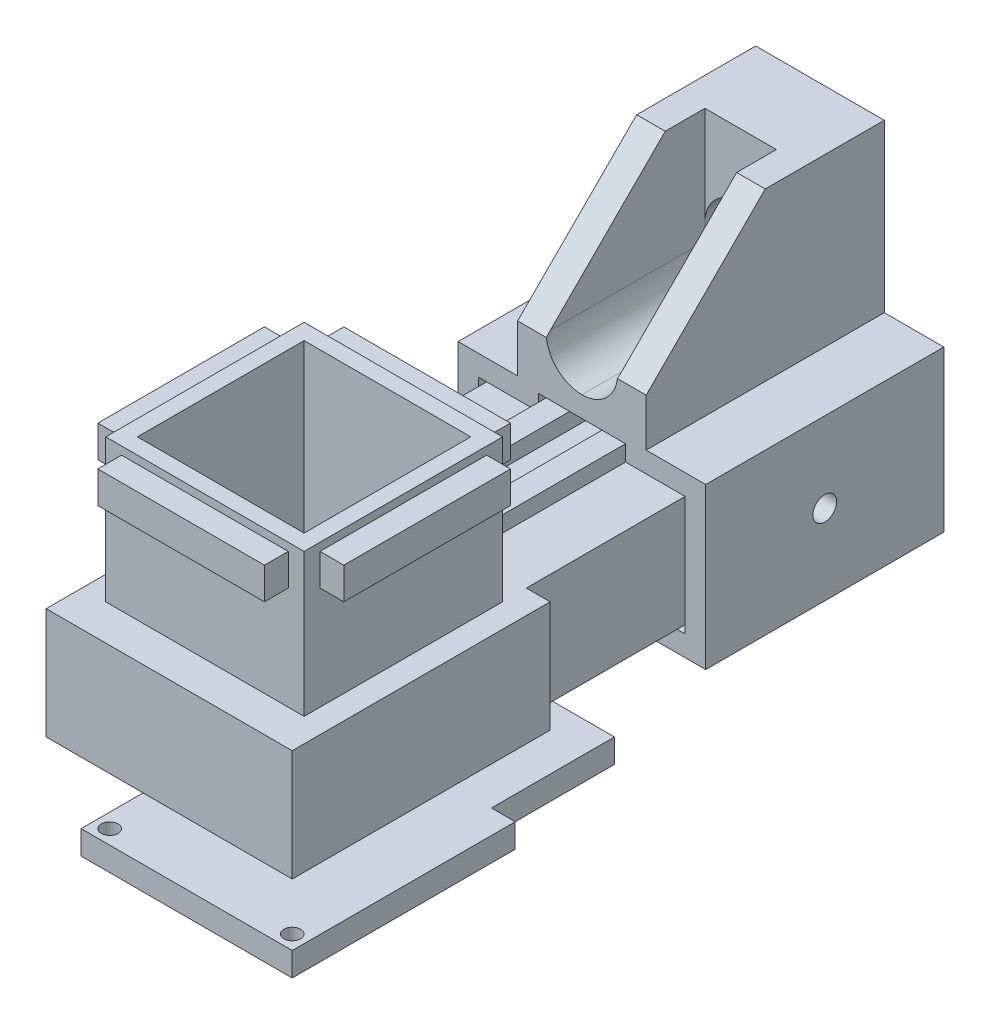
SolidWorks part; units mm, degrees
note: The reader was unsure of these and kept them because the rebuilt part matched: shared geometry of "Sketch2<3>", "Sketch3<7>", "Sketch3<12>", "Sketch3<16>", "Sketch6<3>", "Sketch3<14>", "Sketch14<5>", "Sketch14<7>", "Sketch14<8>".
ref_plane "Front Plane" through (0, 0, 0) normal (0, 0, 1) x (1, 0, 0)
ref_plane "Top Plane" through (0, 0, 0) normal (0, 1, 0) x (1, 0, 0)
ref_plane "Right Plane" through (0, 0, 0) normal (1, 0, 0) x (0, 0, -1)
sketch "Sketch2" plane through (0, 0, 0) normal (0, 1, 0) x (1, 0, 0)
  line L0 (10.5, 10.5) -> (10.5, -10.5)
  line L1 (-12.5, 12.5) -> (12.5, 12.5)
  line L2 (-12.5, 12.5) -> (-12.5, -12.5)
  line L3 (-12.5, -12.5) -> (12.5, -12.5)
  line L4 (12.5, 12.5) -> (12.5, -12.5)
  line L5 (-12.5, 12.5) -> (12.5, -12.5) construction
  line L6 (-12.5, -12.5) -> (12.5, 12.5) construction
  line L7 (-10.5, -10.5) -> (10.5, -10.5)
  line L8 (-10.5, 10.5) -> (-10.5, -10.5)
  line L9 (-10.5, 10.5) -> (10.5, 10.5)
  line L10 (-15.5, 15.5) -> (15.5, 15.5)
  line L11 (15.5, 15.5) -> (15.5, -15.5)
  line L12 (-15.5, -15.5) -> (15.5, -15.5)
  line L13 (-15.5, 15.5) -> (-15.5, -15.5)
  point P0 (0, 0)
  dimension "D1" = 25
  dimension "D2" = 25
  dimension "D3" = 2
  dimension "D4" = 3
extrude "Boss-Extrude1" add sketch "Sketch2" against normal blind 25 contours L4 L1 L2 L3 L8 L9 L0 L7
extrude "Boss-Extrude2" add sketch "Sketch2<3>" against normal blind 4 from offset 1 contours L10 L13 L12 L11 L1 L4 L3 L2 offset against normal yes
sketch "Sketch2<3>" plane through (0, 0, 0) normal (0, 1, 0) x (1, 0, 0) same geometry as "Sketch2"
sketch "Sketch3" plane through (0, -25, 0) normal (0, -1, 0) x (1, 0, 0)
  line L0 (0, 0) -> (0, -22.9057) construction
  line L1 (0, 15) -> (0, 0)
  line L2 (-10.5, 15) -> (10.5, 15)
  line L3 (-10.5, 15) -> (-10.5, -43)
  line L4 (-10.5, -43) -> (10.5, -43)
  line L5 (10.5, 15) -> (10.5, -43)
  line L6 (-12.5, 17) -> (-12.5, -45)
  line L7 (-12.5, -45) -> (12.5, -45)
  line L8 (12.5, 17) -> (12.5, -45)
  line L9 (-12.5, 17) -> (12.5, 17)
  line L10 (-12.5, 17) -> (-15.5, 17)
  line L11 (10.5, -17.5) -> (-10.5, -17.5)
  line L12 (10.5, -17.5) -> (10.5, -10.5)
  line L13 (10.5, -10.5) -> (-10.5, -10.5)
  line L14 (-10.5, -17.5) -> (-10.5, -10.5)
  line L15 (10.5, -17.5) -> (-10.5, -10.5) construction
  line L16 (10.5, -10.5) -> (-10.5, -17.5) construction
  line L19 (-10.5, -28) -> (10.5, -28)
  line L21 (-10.5, 10.5) -> (10.5, 10.5) construction
  line L22 (-10.5, -43) -> (10.5, -43)
  line L23 (-15.5, 17) -> (-15.5, 15.5)
  line L24 (12.5, 17) -> (15.5, 17)
  line L25 (15.5, 17) -> (15.5, 15.5)
  line L28 (15.5, 15.5) -> (-15.5, 15.5)
  line L34 (15.5, -15.5) -> (12.5, -15.5)
  line L35 (-15.5, -15.5) -> (-12.5, -15.5)
  line L36 (-1.5, -10.8377) -> (-1.5, -9.748)
  line L41 (1.5, -18.252) -> (-1.5, -18.252)
  line L42 (1.5, -18.252) -> (1.5, -17.1623)
  line L43 (1.5, -9.748) -> (-1.5, -9.748)
  line L44 (-1.5, -18.252) -> (-1.5, -17.1623)
  line L45 (1.5, -18.252) -> (-1.5, -9.748) construction
  line L46 (1.5, -9.748) -> (-1.5, -18.252) construction
  line L47 (1.5, -10.8377) -> (1.5, -9.748)
  line L48 (-10.5, -43) -> (-10.5, -41)
  line L49 (-10.5, -41) -> (10.5, -41)
  line L50 (10.5, -43) -> (10.5, -41)
  line L51 (-10.5, -43) -> (-8.5, -43)
  line L52 (-10.5, -43) -> (-10.5, -34)
  line L53 (-10.5, -34) -> (-8.5, -34)
  line L54 (-8.5, -43) -> (-8.5, -34)
  line L55 (-10.5, 10.5) -> (10.5, 10.5)
  line L57 (-8.5, -34) -> (-3.5, -34)
  line L58 (-8.5, -34) -> (-8.5, -41)
  line L59 (-8.5, -41) -> (-3.5, -41)
  line L60 (-15.5, -15.5) -> (15.5, -15.5)
  line L61 (15.5, -15.5) -> (15.5, 15.5)
  line L62 (15.5, -15.5) -> (15.5, 15.5)
  line L63 (-15.5, 15.5) -> (-15.5, -15.5)
  line L64 (-15.5, 15.5) -> (-15.5, -15.5)
  line L65 (-3.5, -34) -> (-3.5, -41)
  arc A0 (1.5, -17.1623) -> (1.5, -10.8377) centre (0, -14) ccw
  circle A1 centre (0, 2) radius 1
  arc A3 (-1.5, -10.8377) -> (-1.5, -17.1623) centre (0, -14) ccw
  point P24 (0.7389, -34.4855)
  point P36 (0, -10.5)
  point P46 (-1.5, -10.8377)
  line M11 (12.5, -12.5) -> (12.5, 12.5)
  line M12 (12.5, 12.5) -> (-12.5, 12.5)
  line M13 (-12.5, 12.5) -> (-12.5, -12.5)
  line M14 (-12.5, -12.5) -> (12.5, -12.5)
  line M16 (-10.5, 10.5) -> (10.5, 10.5)
  dimension "D4" = 7
  dimension "D6" = 2
  dimension "D9" = 2
  dimension "D1" = 15
  dimension "D2" = 58
  dimension "D3" = 21
  dimension "D5" = 29
  dimension "D7" = 13
  dimension "D10" = 2
  dimension "D11" = 9
  dimension "D12" = 5
  dimension "D17" = 3
  dimension "D18" = 8.504
  dimension "D8" = 2
  dimension "D16" = 0
extrude "Boss-Extrude4" add sketch "Sketch3" against normal blind 7
extrude "Cut-Extrude2" cut sketch "Sketch3<7>" against normal blind 6 contours L41 L44 A3 L36 L43 L47 A0 L42
sketch "Sketch3<7>" plane through (0, -25, 0) normal (0, -1, 0) x (1, 0, 0) same geometry as "Sketch3"
extrude "Boss-Extrude5" add sketch "Sketch3<12>" along normal blind 4 contours L9 L6 L7 L8 L2 L5 L4 L3 M12 M11 M14 M13 | L3 M12 M13 M14 | L5 M12 M14 M11 | L64 L35 L6 L10 L23 | L34 L62 L25 L24 L8 | L9 L6 L3 L2 L5 L8 M12
sketch "Sketch3<12>" plane through (0, -25, 0) normal (0, -1, 0) x (1, 0, 0) same geometry as "Sketch3"
extrude "Cut-Extrude12" cut sketch "Sketch3<16>" against normal blind 1 contours L3 L55 L1 M16 M12 | L2 L3 L1 M12
sketch "Sketch3<16>" plane through (0, -25, 0) normal (0, -1, 0) x (1, 0, 0) same geometry as "Sketch3"
sketch "Sketch6" plane through (0, -29, 0) normal (0, -1, 0) x (1, 0, 0)
  line L0 (13.5, 15) -> (-13.5, 15)
  line L1 (-13.5, 15) -> (-13.5, -13.5)
  line L2 (-13.5, -13.5) -> (-10.5, -13.5)
  line L3 (-10.5, -13.5) -> (-10.5, -43)
  line L4 (-10.5, -43) -> (10.5, -43)
  line L5 (10.5, -43) -> (10.5, -13.5)
  line L6 (10.5, -13.5) -> (13.5, -13.5)
  line L7 (13.5, -13.5) -> (13.5, 15)
  line L8 (15.5, 17) -> (-15.5, 17)
  line L11 (-12.5, -15.5) -> (-12.5, -45)
  line L12 (-12.5, -45) -> (12.5, -45)
  line L13 (12.5, -45) -> (12.5, -15.5)
  line L16 (15.5, 17) -> (-15.5, 17)
  line L19 (-12.5, -15.5) -> (-12.5, -45)
  line L20 (-12.5, -45) -> (12.5, -45)
  line L21 (12.5, -45) -> (12.5, -15.5)
  line L25 (-13.5, 15) -> (-9.5, 15)
  line L26 (-13.5, 15) -> (-13.5, 11)
  line L27 (-13.5, 11) -> (-9.5, 11)
  line L28 (-9.5, 15) -> (-9.5, 11)
  line L29 (13.5, 15) -> (9.5, 15)
  line L30 (13.5, 15) -> (13.5, 11)
  line L31 (13.5, 11) -> (9.5, 11)
  line L32 (9.5, 15) -> (9.5, 11)
  line L36 (-15.5, 17) -> (-15.5, -15.5)
  line L37 (-15.5, 17) -> (-15.5, -15.5)
  line L38 (-15.5, -15.5) -> (-12.5, -15.5)
  line L39 (-15.5, -15.5) -> (-12.5, -15.5)
  line L40 (-15.5, 17) -> (-15.5, -15.5) construction
  line L41 (-15.5, -15.5) -> (-12.5, -15.5) construction
  line L42 (12.5, -15.5) -> (15.5, -15.5) construction
  line L43 (15.5, -15.5) -> (15.5, 17) construction
  line L44 (12.5, -15.5) -> (15.5, -15.5)
  line L45 (12.5, -15.5) -> (15.5, -15.5)
  line L46 (15.5, -15.5) -> (15.5, 17)
  line L47 (15.5, -15.5) -> (15.5, 17)
  line M17 (10.5, 15) -> (10.5, -43)
  line M18 (10.5, -43) -> (-10.5, -43)
  line M19 (-10.5, -43) -> (-10.5, 15)
  line M20 (-10.5, 15) -> (10.5, 15)
  line M21 (15.5, 17) -> (-15.5, 17)
  line M22 (-15.5, 17) -> (-15.5, -15.5)
  line M23 (-15.5, -15.5) -> (-12.5, -15.5)
  line M24 (-12.5, -15.5) -> (-12.5, -45)
  line M25 (-12.5, -45) -> (12.5, -45)
  line M26 (12.5, -45) -> (12.5, -15.5)
  line M27 (12.5, -15.5) -> (15.5, -15.5)
  line M28 (15.5, -15.5) -> (15.5, 17)
  dimension "D3" = 4
  dimension "D4" = 4
  dimension "D5" = 4
  dimension "D6" = 4
  dimension "D1" = 0
  dimension "D2" = 2
extrude "Boss-Extrude7" add sketch "Sketch6" against normal blind 6 contours L28 L27 M20 M19 | L32 L31 M20 M17
extrude "Boss-Extrude8" add sketch "Sketch6<3>" along normal blind 3 contours L7 L6 L2 L1 L0 M28 M21 M22 M23 M24 M25 M26 M27 M17 M18 M19 M20
sketch "Sketch6<3>" plane through (0, -29, 0) normal (0, -1, 0) x (1, 0, 0) same geometry as "Sketch6"
sketch "Sketch7" plane through (0, -29, 0) normal (0, -1, 0) x (1, 0, 0)
  line L0 (13.5, -13.5) -> (13.5, 15) construction
  line L1 (13.5, 15) -> (9.5, 15) construction
  line L2 (9.5, 15) -> (9.5, 11) construction
  line L3 (9.5, 11) -> (10.5, 11) construction
  line L4 (10.5, 11) -> (10.5, -13.5) construction
  line L5 (10.5, -13.5) -> (13.5, -13.5) construction
  line L6 (-9.5, 11) -> (-9.5, 15) construction
  line L7 (-9.5, 15) -> (-13.5, 15) construction
  line L8 (-13.5, 15) -> (-13.5, -13.5) construction
  line L9 (-13.5, -13.5) -> (-10.5, -13.5) construction
  line L10 (-10.5, -13.5) -> (-10.5, 11) construction
  line L11 (-10.5, 11) -> (-9.5, 11) construction
  line L12 (13.5, -13.5) -> (13.5, 15)
  line L13 (13.5, 15) -> (9.5, 15)
  line L14 (9.5, 15) -> (9.5, 11)
  line L15 (9.5, 11) -> (10.5, 11)
  line L16 (10.5, 11) -> (10.5, -13.5)
  line L17 (10.5, -13.5) -> (13.5, -13.5)
  line L18 (-9.5, 11) -> (-9.5, 15)
  line L19 (-9.5, 15) -> (-13.5, 15)
  line L20 (-13.5, 15) -> (-13.5, -13.5)
  line L21 (-13.5, -13.5) -> (-10.5, -13.5)
  line L22 (-10.5, -13.5) -> (-10.5, 11)
  line L23 (-10.5, 11) -> (-9.5, 11)
  line L24 (-9.5, 11) -> (-13.5, 15) construction
  line L25 (9.5, 11) -> (13.5, 15) construction
  circle A0 centre (-11.5, 13) radius 1.05
  circle A1 centre (11.5, 13) radius 1.05
  dimension "D1" = 2.1
  dimension "D2" = 2.1
extrude "Cut-Extrude9" cut sketch "Sketch7" against normal blind 3 contours A0 | A1
extrude "Cut-Extrude11" cut sketch "Sketch3<14>" against normal blind 3 contours L41 L44 L11 L3 L19 L5 L42 | L54 L49 L5 L19 L3 L53
sketch "Sketch3<14>" plane through (0, -25, 0) normal (0, -1, 0) x (1, 0, 0) same geometry as "Sketch3"
sketch "Sketch10" plane through (0, -25, 0) normal (0, -1, 0) x (1, 0, 0)
  line L1 (10.5, -43) -> (-10.5, -43) construction
  line L6 (-10.5, -34) -> (-8.5, -34)
  line L18 (-10.5, -34) -> (-10.5, -43)
  line L19 (-10.5, -43) -> (-8.5, -43)
  line L21 (-8.5, -34) -> (-8.5, -43)
  line L24 (-3.5, -34) -> (-3.5, -41) construction
  line M11 (-3.5, -34) -> (-10.5, -34)
  line M12 (-10.5, -34) -> (-10.5, -43)
  line M13 (-10.5, -43) -> (10.5, -43)
  dimension "D1" = 5
extrude "Boss-Extrude12" add sketch "Sketch10" along normal up to surface (4 mm away) contours L21 M11 M12 M13 up to face at (-11.5, -29, 11.95)
ref_plane "Plane1" through (0, -42, 0) normal (0, -1, 0) x (-1, 0, 0)
sketch "Sketch8" plane through (0, -42, 0) normal (0, -1, 0) x (-1, 0, 0)
  line L8 (-15.5, 15.5) -> (-15.5, -17)
  line L10 (-15.5, 15.5) -> (-15.5, -17)
  line L12 (-15.5, -17) -> (15.5, -17)
  line L14 (-15.5, -17) -> (15.5, -17)
  line L24 (-13.3, -14.8) -> (13.3, -14.8)
  line L25 (13.3, -14.8) -> (13.3, 13.3)
  line L26 (13.3, 13.3) -> (10.3, 13.3)
  line L27 (10.3, 13.3) -> (10.3, 42.8)
  line L28 (10.3, 42.8) -> (-10.3, 42.8)
  line L29 (-10.3, 42.8) -> (-10.3, 13.3)
  line L30 (-10.3, 13.3) -> (-13.3, 13.3)
  line L31 (-13.3, 13.3) -> (-13.3, -14.8)
  line L32 (15.5, -17) -> (15.5, 15.5)
  line L34 (15.5, -17) -> (15.5, 15.5)
  line L36 (15.5, 15.5) -> (12.5, 15.5)
  line L38 (15.5, 15.5) -> (12.5, 15.5)
  line L40 (12.5, 15.5) -> (12.5, 45)
  line L41 (12.5, 15.5) -> (12.5, 45)
  line L42 (12.5, 45) -> (-12.5, 45)
  line L43 (12.5, 45) -> (-12.5, 45)
  line L44 (-12.5, 45) -> (-12.5, 15.5)
  line L45 (-12.5, 45) -> (-12.5, 15.5)
  line L46 (-12.5, 15.5) -> (-15.5, 15.5)
  line L47 (-12.5, 15.5) -> (-15.5, 15.5)
  line L49 (-10.3, 42.8) -> (6.8, 42.8)
  line L50 (-10.3, 42.8) -> (-10.3, 28.8)
  line L51 (-10.3, 28.8) -> (6.8, 28.8)
  line L60 (6.8, 42.8) -> (6.8, 28.8)
  circle A0 centre (-11.5, -13) radius 1.05 construction
  circle A1 centre (11.5, -13) radius 1.05 construction
  circle A2 centre (-11.5, -13) radius 1.05
  circle A3 centre (11.5, -13) radius 1.05
  dimension "D4" = 14
  dimension "D5" = 3.5
  dimension "D1" = 0
  dimension "D2" = 2.2
extrude "Boss-Extrude9" add sketch "Sketch8" along normal blind 3 separate body contours L28 L60 L51 L29 L30 L31 L24 L25 L26 L27 A3 A2
sketch "Sketch9" plane through (0, 0, -45) normal (0, 0, -1) x (-1, 0, 0)
  line L1 (6.5, -32) -> (-8.5, -32)
  line L2 (6.5, -32) -> (6.5, -26)
  line L3 (6.5, -26) -> (-8.5, -26)
  line L5 (10.5, -32) -> (10.5, -29)
  line L6 (-10.5, -32) -> (10.5, -32)
  line L7 (-10.5, -25) -> (-10.5, -32)
  line L9 (10.5, -32) -> (10.5, -29)
  line L10 (-10.5, -32) -> (10.5, -32)
  line L11 (-10.5, -25) -> (-10.5, -32)
  line L12 (-8.5, -32) -> (-8.5, -26)
  line L17 (8.5, -25) -> (-10.5, -25)
  line L18 (8.5, -25) -> (-10.5, -25)
  line L22 (10.5, -29) -> (8.5, -29)
  line L24 (10.5, -29) -> (8.5, -29)
  line L25 (8.5, -29) -> (8.5, -25)
  line L26 (8.5, -29) -> (8.5, -25)
  line M10 (-12.5, -32) -> (12.5, -32)
  dimension "D2" = 2
  dimension "D3" = 15
  dimension "D4" = 6
  dimension "D1" = 0
extrude "Cut-Extrude10" cut sketch "Sketch9" against normal up to surface (2 mm away) contours L12 L2 L3 M10 up to face at (-2.8333, -28.6667, -43)
sketch "Sketch11" plane through (0, -1, 0) normal (0, 1, 0) x (1, 0, 0)
  line L0 (-12.5, 12.5) -> (-12.5, -12.5) construction
  line L4 (15.5, 15.5) -> (-15.5, 15.5)
  line L5 (-15.5, 15.5) -> (-15.5, -15.5)
  line L6 (-15.5, -15.5) -> (15.5, -15.5)
  line L7 (15.5, -15.5) -> (15.5, 15.5)
  line L8 (15.5, 15.5) -> (-15.5, 15.5)
  line L9 (-15.5, 15.5) -> (-15.5, -15.5)
  line L10 (-15.5, -15.5) -> (15.5, -15.5)
  line L11 (15.5, -15.5) -> (15.5, 15.5)
  line L13 (-15.5, 15.5) -> (-12.5, 15.5)
  line L14 (-15.5, 15.5) -> (-15.5, 10.5)
  line L15 (-15.5, 10.5) -> (-12.5, 10.5)
  line L16 (-12.5, 15.5) -> (-12.5, 10.5)
  line L17 (-12.5, 12.5) -> (12.5, 12.5) construction
  line L18 (-15.5, 15.5) -> (-10.5, 15.5)
  line L19 (-15.5, 15.5) -> (-15.5, 12.5)
  line L20 (-15.5, 12.5) -> (-10.5, 12.5)
  line L21 (-10.5, 15.5) -> (-10.5, 12.5)
  line L22 (15.5, 15.5) -> (12.5, 15.5)
  line L23 (15.5, 15.5) -> (15.5, 10.5)
  line L24 (15.5, 10.5) -> (12.5, 10.5)
  line L25 (12.5, 15.5) -> (12.5, 10.5)
  line L26 (15.5, 15.5) -> (10.5, 15.5)
  line L27 (15.5, 15.5) -> (15.5, 12.5)
  line L28 (15.5, 12.5) -> (10.5, 12.5)
  line L29 (10.5, 15.5) -> (10.5, 12.5)
  line L30 (15.5, -15.5) -> (15.5, -12.5)
  line L31 (15.5, -15.5) -> (10.5, -15.5)
  line L32 (10.5, -15.5) -> (10.5, -12.5)
  line L33 (15.5, -12.5) -> (10.5, -12.5)
  line L34 (15.5, -15.5) -> (15.5, -10.5)
  line L35 (15.5, -15.5) -> (12.5, -15.5)
  line L36 (12.5, -15.5) -> (12.5, -10.5)
  line L37 (15.5, -10.5) -> (12.5, -10.5)
  line L38 (-15.5, -15.5) -> (-12.5, -15.5)
  line L39 (-15.5, -15.5) -> (-15.5, -10.5)
  line L40 (-15.5, -10.5) -> (-12.5, -10.5)
  line L41 (-12.5, -15.5) -> (-12.5, -10.5)
  line L42 (-15.5, -15.5) -> (-10.5, -15.5)
  line L43 (-15.5, -15.5) -> (-15.5, -12.5)
  line L44 (-15.5, -12.5) -> (-10.5, -12.5)
  line L45 (-10.5, -15.5) -> (-10.5, -12.5)
  point P39 (0, 0)
  line M20 (-12.5, 12.5) -> (12.5, 12.5)
  line M21 (12.5, 12.5) -> (12.5, -12.5)
  line M22 (12.5, -12.5) -> (-12.5, -12.5)
  line M23 (-12.5, -12.5) -> (-12.5, 12.5)
  line M24 (15.5, 15.5) -> (-15.5, 15.5)
  line M25 (-15.5, 15.5) -> (-15.5, -15.5)
  line M26 (-15.5, -15.5) -> (15.5, -15.5)
  line M27 (15.5, -15.5) -> (15.5, 15.5)
  dimension "D2" = 5
  dimension "D3" = 5
  dimension "D1" = 0
  dimension "D4" = 4
extrude "Cut-Extrude13" cut sketch "Sketch11" against normal up to surface (4 mm away) contours L44 L39 L41 M26 | L10 L45 L41 M22 | L44 L40 M25 M23 | L10 L36 L32 M22 | L36 L31 L33 M27 | L11 L37 L33 M21 | L20 L14 L15 M23 | L20 L16 L8 M25 | L21 L8 L16 M20 | L8 L29 L25 M20 | L28 L23 L25 M24 | L11 L28 L24 M21 up to face at (0, -5, 0)
sketch "Sketch12" plane through (0, 0, -45) normal (0, 0, -1) x (-1, 0, 0)
  line L0 (0, -32) -> (0, -5.0487) construction
  line L7 (-2.0407, -16) -> (2.0407, -16)
  line L8 (6.5, -26) -> (6.5, -32)
  line L9 (6.5, -32) -> (12.5, -32)
  line L10 (12.5, -32) -> (12.5, -18)
  line L11 (12.5, -18) -> (-12.5, -18)
  line L12 (-12.5, -18) -> (-12.5, -32)
  line L13 (-12.5, -32) -> (-8.5, -32)
  line L14 (-8.5, -32) -> (-8.5, -26)
  line L15 (-8.5, -26) -> (6.5, -26)
  line L16 (6.5, -26) -> (6.5, -32)
  line L17 (6.5, -32) -> (12.5, -32)
  line L18 (12.5, -32) -> (12.5, -18)
  line L19 (12.5, -18) -> (-12.5, -18)
  line L20 (-12.5, -18) -> (-12.5, -32)
  line L21 (-12.5, -32) -> (-8.5, -32)
  line L22 (-8.5, -32) -> (-8.5, -26)
  line L23 (-8.5, -26) -> (6.5, -26)
  line L27 (-2.0407, -16) -> (-2.0407, -18)
  line L28 (-2.0407, -18) -> (2.0407, -18)
  line L29 (2.0407, -16) -> (2.0407, -18)
  line L30 (-2.0407, -16) -> (2.0407, -18) construction
  line L31 (-2.0407, -18) -> (2.0407, -16) construction
  line L32 (-5, -16) -> (5, -16)
  line L33 (-5, -16) -> (-5, -18)
  line L34 (-5, -18) -> (5, -18)
  line L35 (5, -16) -> (5, -18)
  line L36 (-5, -16) -> (5, -18) construction
  line L37 (-5, -18) -> (5, -16) construction
  point P6 (0, -17)
  point P8 (0, -17)
  dimension "D2" = 2
  dimension "D3" = 10
  dimension "D1" = 0
extrude "Boss-Extrude13" add sketch "Sketch12" against normal up to surface (29.5 mm away) up to face at (-14, -25, -15.5)
ref_plane "Plane3" through (0, 0, -65) normal (0, 0, -1) x (-1, 0, 0)
sketch "Sketch13" plane through (0, 0, -65) normal (0, 0, -1) x (-1, 0, 0)
  line L0 (-8.5, -32) -> (6.5, -32)
  line L2 (6.5, -32.5) -> (13, -32.5)
  line L3 (13, -32.5) -> (13, -17.5)
  line L4 (13, -17.5) -> (5.5, -17.5)
  line L5 (-5.1, -10.9) -> (-5, -10.9)
  line L6 (5.5, -17.5) -> (5.5, -15.5)
  line L7 (5.5, -15.5) -> (1.5407, -15.5)
  line L11 (1.5407, -15.5) -> (-5.5, -15.5)
  line L12 (-5.5, -15.5) -> (-5.5, -17.5)
  line L13 (-5.5, -17.5) -> (-13, -17.5)
  line L14 (-13, -17.5) -> (-13, -32.5)
  line L15 (-13, -32.5) -> (-8.5, -32.5)
  line L16 (6.5, -26) -> (6.5, -32)
  line L17 (6.5, -32) -> (12.5, -32)
  line L18 (12.5, -32) -> (12.5, -18)
  line L19 (12.5, -18) -> (5, -18)
  line L20 (5, -18) -> (5, -16)
  line L26 (5, -18) -> (5, -16)
  line L27 (-5, -18) -> (-12.5, -18)
  line L28 (-12.5, -18) -> (-12.5, -32)
  line L29 (-12.5, -32) -> (-8.5, -32)
  line L30 (-8.5, -32) -> (-8.5, -26)
  line L31 (-8.5, -26) -> (6.5, -26)
  line L33 (6.5, -32) -> (12.5, -32)
  line L34 (12.5, -32) -> (12.5, -18)
  line L35 (12.5, -18) -> (5, -18)
  line L43 (-5, -18) -> (-12.5, -18)
  line L44 (-12.5, -18) -> (-12.5, -32)
  line L45 (-12.5, -32) -> (-8.5, -32)
  line L48 (-8.5, -32.5) -> (6.5, -32.5)
  line L49 (6.5, -35.1) -> (15.6, -35.1)
  line L50 (6.5, -32.1) -> (12.6, -32.1)
  line L51 (12.6, -32.1) -> (12.6, -17.9)
  line L52 (12.6, -17.9) -> (5.1, -17.9)
  line L58 (-5.1, -17.9) -> (-12.6, -17.9)
  line L59 (-12.6, -17.9) -> (-12.6, -32.1)
  line L60 (-12.6, -32.1) -> (-8.5, -32.1)
  line L61 (-8.5, -32.1) -> (6.5, -32.1)
  line L62 (6.5, -35.1) -> (15.6, -35.1)
  line L63 (15.6, -35.1) -> (15.6, -14.9)
  line L71 (-15.6, -14.9) -> (-15.6, -35.1)
  line L72 (-15.6, -35.1) -> (-8.5, -35.1)
  line L73 (-8.5, -35.1) -> (6.5, -35.1)
  line L74 (15.6, -35.1) -> (15.6, -14.9)
  line L75 (15.6, -14.9) -> (8.1, -14.9)
  line L76 (8.1, -14.9) -> (8.1, -12.9)
  line L77 (8.1, -12.9) -> (0, -12.9)
  line L78 (0, -12.9) -> (0, -12.9)
  line L79 (0, -12.9) -> (0, -12.9)
  line L80 (0, -12.9) -> (0, -12.9)
  line L81 (0, -12.9) -> (-8.1, -12.9)
  line L82 (-8.1, -12.9) -> (-8.1, -14.9)
  line L83 (-8.1, -14.9) -> (-15.6, -14.9)
  line L84 (-15.6, -14.9) -> (-15.6, -35.1)
  line L85 (-15.6, -35.1) -> (-8.5, -35.1)
  line L86 (-8.5, -35.1) -> (6.5, -35.1)
  line L87 (-1.5407, -15.5) -> (-5.5, -15.5) construction
  line L90 (5, -18) -> (5, -13) construction
  line L91 (5, -13) -> (3, -13) construction
  line L92 (-3, -13) -> (-5, -13) construction
  line L93 (-5, -13) -> (-5, -18) construction
  line L94 (5, -16) -> (2.0407, -16)
  line L95 (5, -16) -> (2.0407, -16)
  line L96 (2.0407, -16) -> (2.0407, -18)
  line L97 (2.0407, -16) -> (2.0407, -18)
  line L98 (2.0407, -18) -> (-2.0407, -18)
  line L99 (2.0407, -18) -> (-2.0407, -18)
  line L100 (-2.0407, -18) -> (-2.0407, -16)
  line L101 (-2.0407, -18) -> (-2.0407, -16)
  line L102 (-2.0407, -16) -> (-5, -16)
  line L103 (-2.0407, -16) -> (-5, -16)
  line L104 (-5, -16) -> (-5, -18)
  line L105 (-5, -16) -> (-5, -18)
  line L106 (-8.1, -9.9) -> (-8.1, -14.9) construction
  line L107 (-3, -9.9) -> (-8.1, -9.9) construction
  line L108 (-3, -9.9) -> (3, -9.9) construction
  line L109 (8.1, -9.9) -> (3, -9.9) construction
  line L110 (8.1, -14.9) -> (8.1, -9.9) construction
  line L111 (-3, -13) -> (3, -13) construction
  line L112 (5.1, -17.9) -> (5.1, -12.9) construction
  line L113 (5.1, -12.9) -> (3, -12.9) construction
  line L114 (-3, -12.9) -> (3, -12.9) construction
  line L115 (-3, -12.9) -> (-5.1, -12.9) construction
  line L116 (-5.1, -12.9) -> (-5.1, -17.9) construction
  line L117 (-8.1, -14.9) -> (-15.6, -14.9) construction
  line L118 (15.6, -14.9) -> (8.1, -14.9) construction
  line L119 (1.5407, -17.5) -> (-1.5407, -17.5) construction
  line L120 (1.5407, -15.5) -> (1.5407, -17.5) construction
  line L121 (-1.5407, -17.5) -> (-1.5407, -15.5) construction
  dimension "D1" = 0
  dimension "D2" = 0.1
  dimension "D3" = 3.1
  dimension "D4" = 0.5
  dimension "D5" = 3.1
extrude "Boss-Extrude14" add sketch "Sketch13" against normal blind 30 separate body
sketch "Sketch14" plane through (0, 0, -65) normal (0, 0, -1) x (-1, 0, 0)
  line L0 (0, -4.9) -> (0, 10.1531) construction
  line L1 (0, -6.4) -> (4.5, -6.4) construction
  line L3 (-8.1, 6.1) -> (8.1, 6.1)
  line L4 (-8.1, 6.1) -> (-8.1, -12.9)
  line L5 (-8.1, -12.9) -> (8.1, -12.9)
  line L6 (8.1, 6.1) -> (8.1, -12.9)
  line L7 (-8.1, 6.1) -> (8.1, -12.9) construction
  line L8 (-15.6, -35.1) -> (15.6, -35.1)
  line L9 (15.6, -35.1) -> (15.6, -14.9)
  line L10 (-8.1, -12.9) -> (-8.1, -14.9)
  line L11 (-8.1, -12.9) -> (-8.1, -14.9)
  line L12 (-8.1, -14.9) -> (-15.6, -14.9)
  line L13 (-8.1, -14.9) -> (-15.6, -14.9)
  line L14 (15.6, -14.9) -> (8.1, -14.9)
  line L15 (-15.6, -14.9) -> (-15.6, -35.1)
  line L16 (-15.6, -35.1) -> (15.6, -35.1)
  line L17 (15.6, -35.1) -> (15.6, -14.9)
  line L23 (-15.6, -14.9) -> (-15.6, -35.1)
  line L24 (-8.1, -12.9) -> (8.1, 6.1) construction
  line L32 (15.6, -14.9) -> (8.1, -14.9)
  line L33 (8.1, -14.9) -> (8.1, -12.9)
  line L34 (8.1, -14.9) -> (8.1, -12.9)
  line L35 (8.1, -12.9) -> (-8.1, -12.9)
  line L36 (8.1, -12.9) -> (-8.1, -12.9)
  circle A0 centre (0, -6.4) radius 2.6
  circle A1 centre (0, -6.4) radius 4.5
  circle A2 centre (4.5, -6.4) radius 1.1
  circle A3 centre (-4.5, -6.4) radius 1.1
  point P19 (0, -3.4)
  dimension "D2" = 5.2
  dimension "D3" = 9
  dimension "D4" = 2.2
  dimension "D5" = 4.5
  dimension "D6" = 16.2
  dimension "D7" = 12.5
  dimension "D8" = 6.5
  dimension "D1" = 0
extrude "Boss-Extrude16" add sketch "Sketch14" against normal blind 10 contours L4 L3 L6 L5
extrude "Cut-Extrude14" cut sketch "Sketch14<5>" against normal blind 3 contours A3 A1 | A3 A1 | A1 A2 | A1 A2
sketch "Sketch14<5>" plane through (0, 0, -65) normal (0, 0, -1) x (-1, 0, 0) same geometry as "Sketch14"
extrude "Cut-Extrude15" cut sketch "Sketch14<7>" against normal up to surface (10 mm away) contours A0 up to face at (0, -3.4, -55)
sketch "Sketch14<7>" plane through (0, 0, -65) normal (0, 0, -1) x (-1, 0, 0) same geometry as "Sketch14"
extrude "Cut-Extrude16" cut sketch "Sketch14<8>" along normal offset from surface (6 mm away) 4 from surface at -10 contours A1 A3 A2 A0 | A3 A1 | A1 A2
sketch "Sketch14<8>" plane through (0, 0, -65) normal (0, 0, -1) x (-1, 0, 0) same geometry as "Sketch14"
sketch "Sketch15" plane through (0, -1, 0) normal (0, 1, 0) x (1, 0, 0)
  line L0 (12.5, 10.5) -> (12.5, -10.5)
  line L1 (12.5, 0) -> (15.5, 0) construction
  line L4 (12.5, -10.5) -> (15.5, -10.5)
  line L5 (15.5, -10.5) -> (15.5, 10.5)
  line L6 (15.5, 10.5) -> (12.5, 10.5)
  line L7 (12.5, 10.5) -> (12.5, -10.5)
  line L8 (12.5, -10.5) -> (15.5, -10.5)
  line L9 (15.5, -10.5) -> (15.5, 10.5)
  line L10 (15.5, 10.5) -> (12.5, 10.5)
  line L11 (12.5, 10.5) -> (12.5, -10.5)
  line L14 (-1.5, -12.5) -> (-4.5, -12.5)
  line L15 (12.5, -1.5) -> (15.5, -1.5)
  line L21 (12.5, -1.5) -> (12.5, 1.5)
  line L22 (12.5, 1.5) -> (15.5, 1.5)
  line L58 (15.5, -1.5) -> (15.5, 1.5)
  line L59 (12.5, -1.5) -> (15.5, 1.5) construction
  line L60 (12.5, 1.5) -> (15.5, -1.5) construction
  line L61 (12.5, 1.5) -> (15.5, 1.5)
  line L62 (12.5, 1.5) -> (12.5, 4.5)
  line L63 (12.5, 4.5) -> (15.5, 4.5)
  line L64 (15.5, 1.5) -> (15.5, 4.5)
  line L65 (12.5, -1.5) -> (15.5, -1.5)
  line L66 (12.5, -1.5) -> (12.5, -4.5)
  line L67 (12.5, -4.5) -> (15.5, -4.5)
  line L68 (15.5, -1.5) -> (15.5, -4.5)
  line L69 (-1.5, -12.5) -> (-1.5, -15.5)
  line L70 (-1.5, -15.5) -> (-4.5, -15.5)
  line L71 (-4.5, -12.5) -> (-4.5, -15.5)
  line L72 (1.5, -12.5) -> (4.5, -12.5)
  line L73 (1.5, -12.5) -> (1.5, -15.5)
  line L74 (1.5, -15.5) -> (4.5, -15.5)
  line L75 (4.5, -12.5) -> (4.5, -15.5)
  line L76 (-12.5, 1.5) -> (-12.5, 4.5)
  line L77 (-12.5, 1.5) -> (-15.5, 1.5)
  line L78 (-15.5, 1.5) -> (-15.5, 4.5)
  line L79 (-12.5, 4.5) -> (-15.5, 4.5)
  line L80 (-12.5, -1.5) -> (-12.5, -4.5)
  line L81 (-12.5, -1.5) -> (-15.5, -1.5)
  line L82 (-15.5, -1.5) -> (-15.5, -4.5)
  line L83 (-12.5, -4.5) -> (-15.5, -4.5)
  line L84 (1.5, 12.5) -> (4.5, 12.5)
  line L85 (1.5, 12.5) -> (1.5, 15.5)
  line L86 (1.5, 15.5) -> (4.5, 15.5)
  line L87 (4.5, 12.5) -> (4.5, 15.5)
  line L88 (-1.5, 12.5) -> (-4.5, 12.5)
  line L89 (-1.5, 12.5) -> (-1.5, 15.5)
  line L90 (-1.5, 15.5) -> (-4.5, 15.5)
  line L91 (-4.5, 12.5) -> (-4.5, 15.5)
  point P2 (0, 0)
  point P4 (14, 0)
  point P46 (0, 0)
  point P49 (0, 0)
  dimension "D3" = 3
  dimension "D4" = 3
  dimension "D5" = 3
  dimension "D1" = 0
  dimension "D6" = 4
extrude "Boss-Extrude17" [suppressed] add sketch "Sketch15" along normal blind 3
sketch "Sketch18" plane through (0, 0, -55) normal (0, 0, 1) x (1, 0, 0)
  line L0 (8.1, 6.1) -> (-8.1, 6.1) construction
  line L1 (-8.1, -12.9) -> (-4.5, -12.9)
  line L2 (-8.1, -12.9) -> (-8.1, 6.1)
  line L3 (-8.1, 6.1) -> (-4.5, 6.1)
  line L4 (-4.5, -12.9) -> (-4.5, 6.1)
  line L6 (8.1, -12.9) -> (4.5, -12.9)
  line L7 (8.1, -12.9) -> (8.1, 6.1)
  line L8 (8.1, 6.1) -> (4.5, 6.1)
  line L9 (4.5, -12.9) -> (4.5, 6.1)
  circle A0 centre (0, -6.4) radius 4.5 construction
  circle A1 centre (0, -6.4) radius 4.5
  line M10 (-8.1, -12.9) -> (8.1, -12.9)
  line M12 (-8.1, -12.9) -> (8.1, -12.9)
  line M13 (8.1, -12.9) -> (8.1, 6.1)
  line M14 (8.1, 6.1) -> (-8.1, 6.1)
  line M15 (-8.1, 6.1) -> (-8.1, -12.9)
extrude "Boss-Extrude18" add sketch "Sketch18" along normal blind 20 contours L4 M10 M14 M15 | L9 M12 M13 M14
chamfer "Chamfer1" distance 15 angle 45 2 edges at (-6.3, 6.1, -35) (6.3, 6.1, -35)
fillet "Fillet1" radius 4.5 2 edges at (4.5, -12.9, -45) (-4.5, -12.9, -45)
sketch "Sketch19" plane through (15.6, 0, 0) normal (1, 0, 0) x (0, 0, -1)
  line L0 (65, -14.9) -> (35, -35.1) construction
  line L4 (65, -35.1) -> (65, -14.9)
  line L5 (65, -14.9) -> (35, -14.9)
  line L6 (35, -14.9) -> (35, -35.1)
  line L7 (35, -35.1) -> (65, -35.1)
  line L8 (65, -35.1) -> (65, -14.9)
  line L9 (65, -14.9) -> (35, -14.9)
  line L10 (35, -14.9) -> (35, -35.1)
  line L11 (35, -35.1) -> (65, -35.1)
  circle A0 centre (50, -25) radius 1.5
  dimension "D2" = 3
  dimension "D1" = 0
extrude "Cut-Extrude17" cut sketch "Sketch19" against normal blind 35 contours A0
